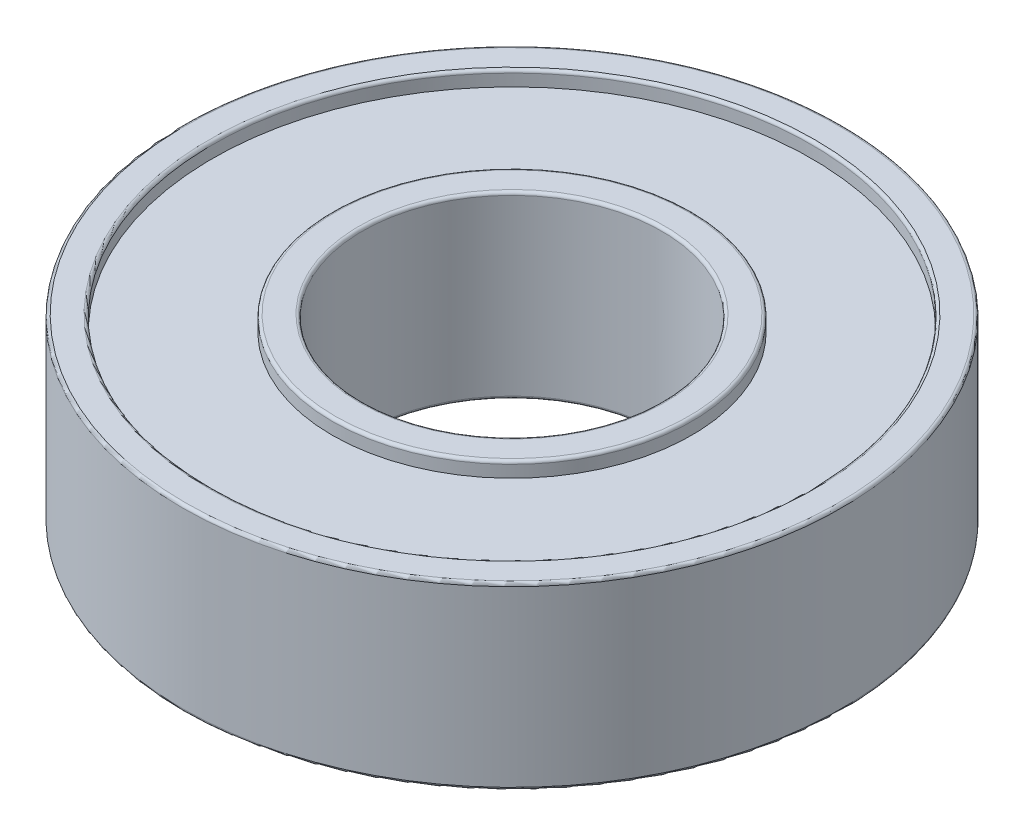
SolidWorks part; units mm, degrees
material "AISI 1045 钢，冷拔"
ref_plane "前视基准面" through (0, 0, 0) normal (0, 0, 1) x (1, 0, 0)
ref_plane "上视基准面" through (0, 0, 0) normal (0, 1, 0) x (1, 0, 0)
ref_plane "右视基准面" through (0, 0, 0) normal (1, 0, 0) x (0, 0, -1)
ref_plane "基准面1" through (0, 0, 0) normal (0, 0, -1) x (-1, 0, 0)
sketch "草图1" plane through (0, 0, 0) normal (0, 0, -1) x (-1, 0, 0)
  line L0 (-5.1, 3) -> (-5.9, 3)
  line L1 (-6, 2.9) -> (-6, 2.5)
  line L2 (-6, 2.5) -> (-10, 2.5)
  line L3 (-10, 2.5) -> (-10, 2.9)
  line L4 (-10.1, 3) -> (-10.9, 3)
  line L5 (-11, 2.9) -> (-11, -2.9)
  line L6 (-10.9, -3) -> (-10.1, -3)
  line L7 (-10, -2.9) -> (-10, -2.5)
  line L8 (-10, -2.5) -> (-6, -2.5)
  line L9 (-6, -2.5) -> (-6, -2.9)
  line L10 (-5.9, -3) -> (-5.1, -3)
  line L11 (-5, -2.9) -> (-5, 2.9)
  line L12 (0, -3) -> (0, 3) construction
  arc A0 (-5.9, 3) -> (-6, 2.9) centre (-5.9, 2.9) ccw
  arc A1 (-10, 2.9) -> (-10.1, 3) centre (-10.1, 2.9) ccw
  arc A2 (-10.9, 3) -> (-11, 2.9) centre (-10.9, 2.9) ccw
  arc A3 (-11, -2.9) -> (-10.9, -3) centre (-10.9, -2.9) ccw
  arc A4 (-10.1, -3) -> (-10, -2.9) centre (-10.1, -2.9) ccw
  arc A5 (-6, -2.9) -> (-5.9, -3) centre (-5.9, -2.9) ccw
  arc A6 (-5.1, -3) -> (-5, -2.9) centre (-5.1, -2.9) ccw
  arc A7 (-5, 2.9) -> (-5.1, 3) centre (-5.1, 2.9) ccw
revolve "旋转1" add sketch "草图1" angle 360 about L12 reverse direction yes
